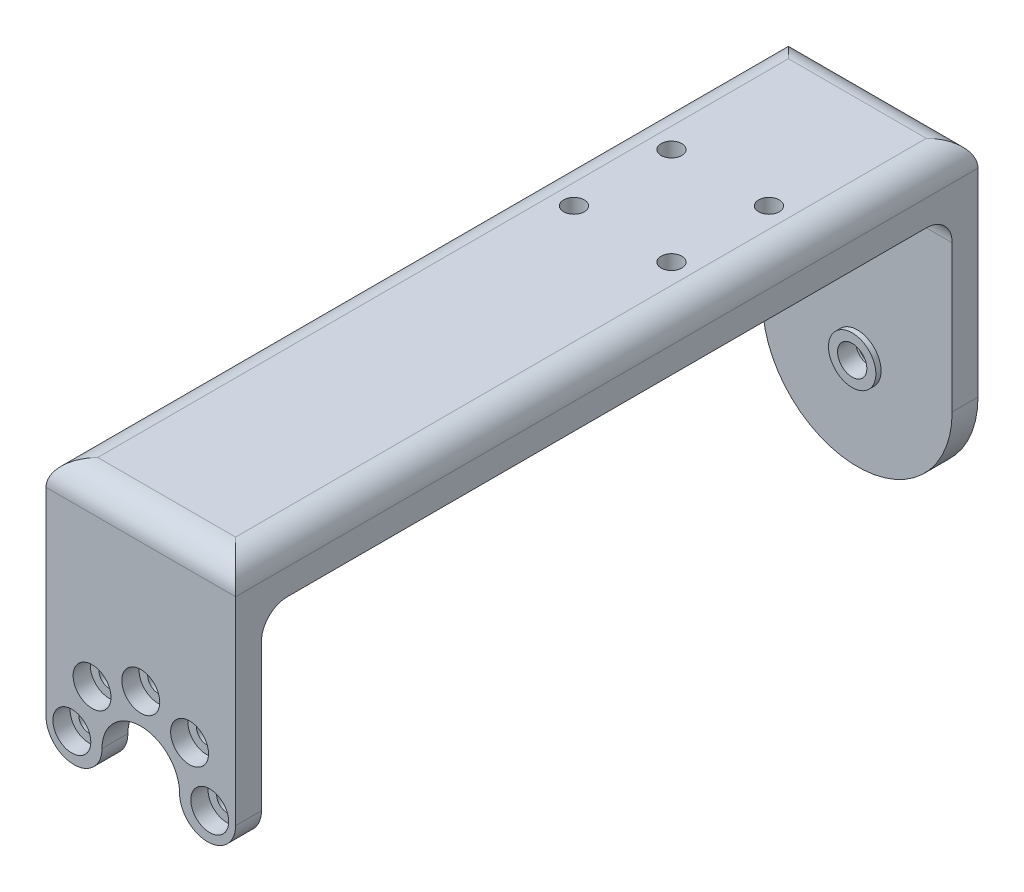
SolidWorks part; units mm, degrees
ref_plane "Plano frontal" through (0, 0, 0) normal (0, 0, 1) x (1, 0, 0)
ref_plane "Plano superior" through (0, 0, 0) normal (0, 1, 0) x (1, 0, 0)
ref_plane "Plano direito" through (0, 0, 0) normal (1, 0, 0) x (0, 0, -1)
sketch "Esboço1" plane through (0, 0, 0) normal (0, 0, 1) x (1, 0, 0)
  line L0 (11, 0) -> (11, 23)
  line L1 (11, 23) -> (-11, 23)
  line L2 (-11, 23) -> (-11, 0)
  arc A3 (11, 0) -> (4.5, 0) centre (7.75, 0) cw
  arc A8 (4.5, 0) -> (-4.5, 0) centre (0, 0) ccw
  arc A10 (-4.5, 0) -> (-11, 0) centre (-7.75, 0) cw
  dimension "D1" = 23
extrude "Ressalto-extrusão1" add sketch "Esboço1" along normal blind 3
sketch "Esboço2" plane through (0, 23, 0) normal (0, 1, 0) x (1, 0, 0)
  line L0 (11, -3) -> (11, 0) construction
  line L1 (-11, -3) -> (11, -3)
  line L2 (-11, -3) -> (-11, 83.15)
  line L3 (-11, 83.15) -> (11, 83.15)
  line L4 (11, -3) -> (11, 83.15)
  line L5 (11, -3) -> (-11, -3) construction
  point P7 (0, -3)
  point P8 (0, -3)
  dimension "D1" = 86.15
extrude "Ressalto-extrusão2" add sketch "Esboço2" along normal blind 3
ref_plane "Plano2" through (0, 0, -80.15) normal (0, 0, -1) x (-1, 0, 0)
sketch "Esboço3" plane through (0, 0, -80.15) normal (0, 0, -1) x (-1, 0, 0)
  line L1 (-11, 0) -> (-11, 23)
  line L2 (-11, 23) -> (11, 23)
  line L3 (11, 23) -> (11, 0)
  arc A0 (-11, 0) -> (11, 0) centre (0, 0) ccw
  dimension "D1" = 22
extrude "Ressalto-extrusão3" add sketch "Esboço3" along normal blind 3
hole_wizard "Rebaixo para SHCS M21" positions "Esboço4" profile "Esboço5" counterbore size "M2" standard "Ansi Metric" end condition up to next
sketch "Esboço4" plane through (0, 0, 3) normal (0, 0, 1) x (1, 0, 0)
  arc A0 (8.8, 0) -> (7.2, 0) centre (8, 0) ccw construction
  point P0 (8, 0)
sketch "Esboço5" plane through (8, 0, 3) normal (1, 0, 0) x (0, -1, 0)
  line L0 (0, 0) -> (0, 3)
  line L1 (0, 3) -> (1.2, 3)
  line L3 (1.2, 3) -> (1.2, 2)
  line L4 (1.2, 2) -> (2.2, 2)
  line L5 (2.2, 2) -> (2.2, 0)
  line L7 (2.2, 0) -> (0, 0)
  line L11 (0, -6.35) -> (0, 107.95) construction
  dimension "Thru Hole Dia." = 2.4
  dimension "Thru Hole Depth" = 3
  dimension "C'Bore Dia." = 4.4
  dimension "C'Bore Depth" = 2
pattern_circular "PadrãoCircular1" count 5 every 45 about axis through (0, 0, 3) along (0, 0, -1) of "Rebaixo para SHCS M21" reverse direction yes
sketch "Esboço10" plane through (0, 0, -80.15) normal (0, 0, 1) x (1, 0, 0)
  circle A0 centre (0, 0) radius 2.75
  circle A2 centre (0, 0) radius 3.25 construction
  dimension "D1" = 0.5
extrude "Ressalto-extrusão4" add sketch "Esboço10" along normal blind 0.6 contours A0
hole_wizard "Rebaixo para parafuso com cabeça panela de M31" positions "Esboço11" profile "Esboço12" counterbore size "M3" standard "DIN" end condition up to next
sketch "Esboço11" plane through (0, 0, -83.15) normal (0, 0, -1) x (-1, 0, 0)
  circle A0 centre (0, 0) radius 3.25 construction
  point P0 (0, 0)
sketch "Esboço12" plane through (0, 0, -83.15) normal (1, 0, 0) x (0, 1, 0)
  line L0 (0, 0) -> (0, 3.6)
  line L1 (0, 3.6) -> (1.7, 3.6)
  line L3 (1.7, 3.6) -> (1.7, 1.5)
  line L4 (1.7, 1.5) -> (3.5, 1.5)
  line L5 (3.5, 1.5) -> (3.5, 0)
  line L7 (3.5, 0) -> (0, 0)
  line L11 (0, -6.35) -> (0, 107.95) construction
  dimension "Thru Hole Dia." = 3.4
  dimension "Thru Hole Depth" = 3.6
  dimension "C'Bore Dia." = 7
  dimension "C'Bore Depth" = 1.5
ref_plane "Plano3" through (0, 0, -40.075) normal (0, 0, -1) x (-1, 0, 0)
sketch "Esboço14" plane through (-11, 0, 0) normal (-1, 0, 0) x (0, 0, 1)
  line L0 (3, 26) -> (3, 0) construction
  line L1 (-83.15, 26) -> (3, 26)
  line L2 (-83.15, 26) -> (-83.15, 20)
  line L3 (-83.15, 20) -> (3, 20)
  line L4 (3, 26) -> (3, 20)
  line L5 (-80.15, 23) -> (0, 23) construction
  dimension "D1" = 3
extrude "Ressalto-extrusão5" add sketch "Esboço14" against normal blind 3
mirror "Espelhar2" about plane through (0, 0, 0) normal (1, 0, 0) of "Ressalto-extrusão5"
hole_wizard "Rebaixo para parafuso com cabeça redonda de M21" positions "Esboço16" profile "Esboço17" counterbore size "M2" standard "DIN" end condition up to next
sketch "Esboço16" plane through (0, 23, 0) normal (0, -1, 0) x (-1, 0, 0)
  line L0 (0, 58.5796) -> (5.6569, 64.2364) construction
  line L2 (0, 58.5796) -> (25.8, 58.5796) construction
  line L3 (25.8, 67.0796) -> (25.8, 50.0796) construction
  line L4 (25.8, 67.0796) -> (25.8, 50.0796) construction
  line L5 (-11, 83.15) -> (11, 83.15) construction
  line L6 (0, 58.5796) -> (-5.6569, 52.9227) construction
  point P0 (5.6569, 64.2364)
  point P25 (5.6569, 52.9227)
  point P26 (-5.6569, 52.9227)
  point P27 (-5.6569, 64.2364)
  point P42 (0, 83.15)
  dimension "D1" = 45
  dimension "D2" = 8
  dimension "D3" = 4
sketch "Esboço17" plane through (-5.6569, 23, -64.2364) normal (1, 0, 0) x (0, 0, -1)
  line L0 (0, 0) -> (0, 3)
  line L1 (0, 3) -> (1.2, 3)
  line L3 (1.2, 3) -> (1.2, 1)
  line L4 (1.2, 1) -> (2.2, 1)
  line L5 (2.2, 1) -> (2.2, 0)
  line L7 (2.2, 0) -> (0, 0)
  line L11 (0, -6.35) -> (0, 107.95) construction
  dimension "Thru Hole Dia." = 2.4
  dimension "Thru Hole Depth" = 3
  dimension "C'Bore Dia." = 4.4
  dimension "C'Bore Depth" = 1
fillet "Filete2" radius 3 4 edges at (9.5, 20, -80.15) (9.5, 20, 0) (-9.5, 20, -80.15) (-9.5, 20, 0)
fillet "Filete1" radius 3 8 edges at (8, 23, -40.075) (0, 23, -80.15) (-8, 23, -40.075) (0, 23, 0) (11, 26, -40.075) (0, 26, 3) (-11, 26, -40.075) (0, 26, -83.15)
